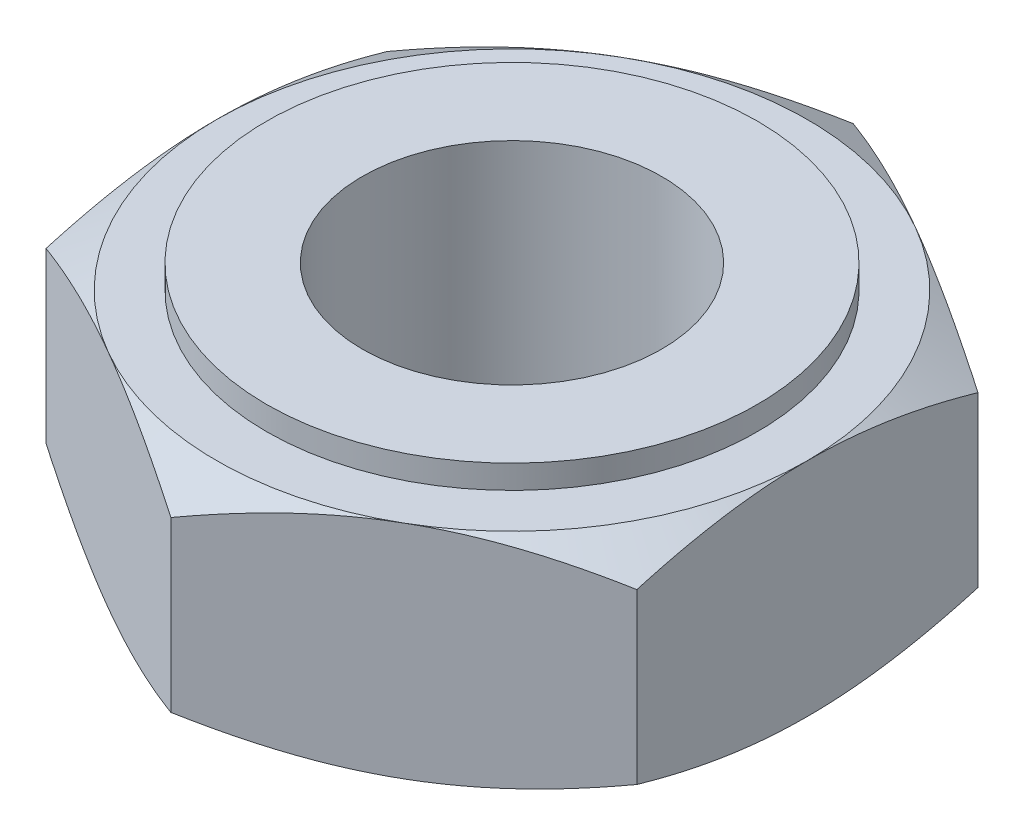
SolidWorks part; units mm, degrees
material "Nylon 101"
ref_plane "Front Plane" through (0, 0, 0) normal (0, 0, 1) x (1, 0, 0)
ref_plane "Top Plane" through (0, 0, 0) normal (0, 1, 0) x (1, 0, 0)
ref_plane "Right Plane" through (0, 0, 0) normal (1, 0, 0) x (0, 0, -1)
sketch "Sketch1" plane through (0, 0, 0) normal (0, 1, 0) x (1, 0, 0)
  line L1 (-4.7625, 2.7496) -> (-4.7625, -2.7496)
  line L2 (-4.7625, -2.7496) -> (0, -5.4993)
  line L3 (0, -5.4993) -> (4.7625, -2.7496)
  line L4 (4.7625, -2.7496) -> (4.7625, 2.7496)
  line L5 (4.7625, 2.7496) -> (0, 5.4993)
  line L6 (0, 5.4993) -> (-4.7625, 2.7496)
  circle A0 centre (0, 0) radius 4.7625 construction
  circle A1 centre (0, 0) radius 2.413
  dimension "Thread Size" = 4.826
  dimension "Hex" = 9.525
extrude "Boss-Extrude1" add sketch "Sketch1" along normal mid plane 3.5719
sketch "Sketch2" plane through (0, 1.7859, 0) normal (0, 1, 0) x (1, 0, 0)
  circle A0 centre (0, 0) radius 2.413 construction
  circle A1 centre (0, 0) radius 2.413
curve "Helix/Spiral1" pitch 1.0583 height 4.6302 turns 4.375 parameters "Pitch"=1.0583
sketch "Sketch6" plane through (0, 1.7859, 0) normal (0, 1, 0) x (1, 0, 0)
  line L0 (0, -2.413) -> (0, -5.4993) construction
  circle A0 centre (0, 0) radius 2.413 construction
  circle A1 centre (0, 0) radius 2.413
  circle A2 centre (0, 0) radius 3.9561
  point P7 (0, -3.9561)
extrude "Boss-Extrude2" add sketch "Sketch6" along normal blind 0.381
sketch "Sketch3" plane through (0, 0, 0) normal (1, 0, 0) x (0, 0, -1)
  line L0 (1.7256, 2.3151) -> (2.413, 2.712)
  line L1 (2.413, 2.712) -> (2.413, 1.7859)
  line L2 (2.413, 1.7859) -> (1.7256, 2.1828)
  line L3 (1.7256, 2.1828) -> (1.7256, 2.3151)
  line L4 (2.0693, 2.5135) -> (2.0693, 1.9844) construction
  line L5 (1.7256, 2.249) -> (2.413, 2.249) construction
  line L6 (2.413, 1.7859) -> (-2.413, 1.7859) construction
  dimension "D1" = 60
  dimension "D2" = 0.1323
  dimension "D3" = 0.5292
sweep "Sweep1" [suppressed] add profiles "Sketch3" path "Helix/Spiral1"
sketch "Sketch4" plane through (0, 1.7859, 0) normal (0, 1, 0) x (1, 0, 0)
  circle A1 centre (0, 0) radius 2.413
  circle A2 centre (0, 0) radius 2.413
  dimension "D1" = 0
extrude "Cut-Extrude1" [suppressed] cut sketch "Sketch4" along normal through all and the other way through all draft 45
sketch "Sketch5" plane through (0, 1.7859, 0) normal (0, 1, 0) x (1, 0, 0)
  circle A0 centre (0, 0) radius 4.7625 construction
  circle A1 centre (0, 0) radius 4.7625
extrude "Cut-Extrude2" cut sketch "Sketch5" against normal through all draft 60 flip side to cut
mirror "Mirror1" about plane through (0, 0, 0) normal (0, 1, 0) of "Cut-Extrude2", "Cut-Extrude1"
equation "\"D2@Sketch3\" = \"Pitch@Helix/Spiral1\"*.125"
equation "\"D3@Sketch3\" = \"Pitch@Helix/Spiral1\"*.5"
equation "\"D3@Helix/Spiral1\" = \"Height@Boss-Extrude1\"+\"Pitch@Helix/Spiral1\""
